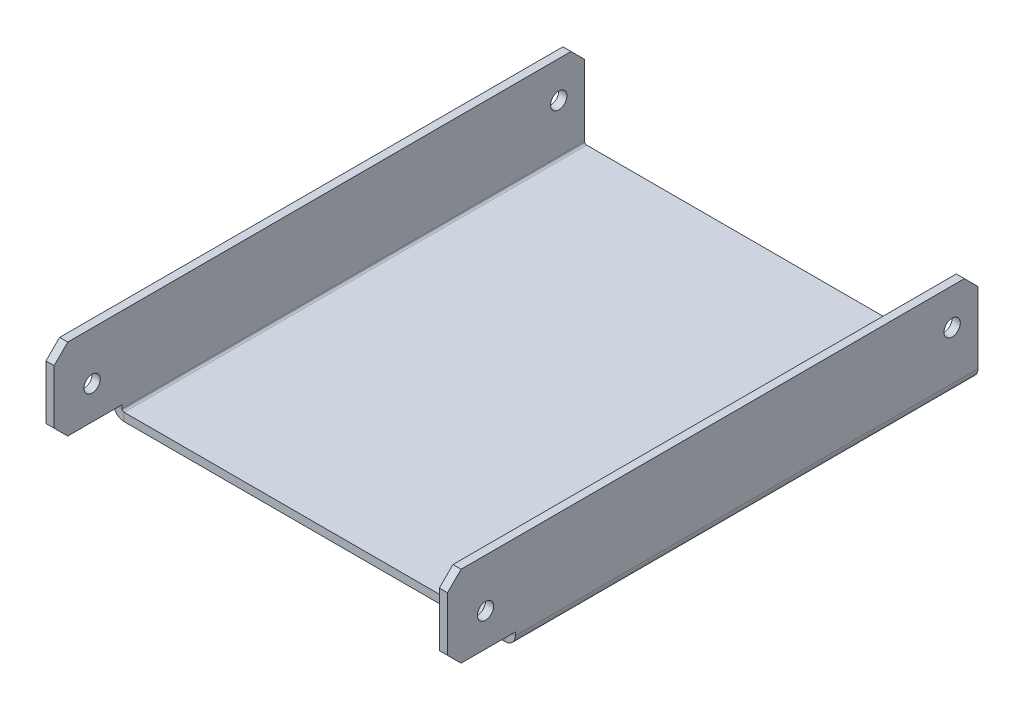
SolidWorks part; units mm, degrees
note: The reader was unsure of these and kept them because the rebuilt part matched: flange length of "Edge-Flange1".
ref_plane "정면" through (0, 0, 0) normal (0, 0, 1) x (1, 0, 0)
ref_plane "윗면" through (0, 0, 0) normal (0, 1, 0) x (1, 0, 0)
ref_plane "우측면" through (0, 0, 0) normal (1, 0, 0) x (0, 0, -1)
sketch "Sketch18" plane through (0, 0, 0) normal (0, 1, 0) x (1, 0, 0)
  line L1 (-148, -166.3369) -> (0, -166.3369)
  line L2 (-148, -166.3369) -> (-148, 39.1965)
  line L3 (-148, 39.1965) -> (0, 39.1965)
  line L4 (0, -166.3369) -> (0, 39.1965)
  dimension "D1" = 205.5334
  dimension "D2" = 148
base flange "Base-Flange1" sketch "Sketch18" thickness 3 reverse thickness direction no parameters "D1"=0.7366
edge flange "Edge-Flange1" sketch "Sketch25" flange profiles "Sketch25", "Sketch26" flange angle 90 flange length 35 flange position material inside bend radius 0.7366 thickness 3 relief rectangular parameters "D6"=10, "D8"=1
sketch "Sketch25" plane through (0, 0, 0) normal (-1, 0, 0) x (0, 0, 1)
  line L2 (-39.1965, 0) -> (-39.1965, 32)
  line L3 (-39.1965, 32) -> (166.3369, 32)
  line L4 (166.3369, 32) -> (166.3369, 0)
  line L14 (166.3369, 0) -> (-39.1965, 0) construction
  line L15 (166.3369, 0) -> (-39.1965, 0)
sketch "Sketch26" plane through (-148, 0, 0) normal (1, 0, 0) x (0, 0, -1)
  line L2 (-166.3369, 0) -> (-166.3369, 32)
  line L3 (-166.3369, 32) -> (39.1965, 32)
  line L4 (39.1965, 32) -> (39.1965, 0)
  line L10 (39.1965, 0) -> (-166.3369, 0) construction
  line L11 (39.1965, 0) -> (-166.3369, 0)
bend "EdgeBend1" bend radius 0.7366 bend angle 90 parameters "D5"=1
bend "EdgeBend2" bend radius 0.7366 bend angle 90 parameters "D5"=2
sketch "Sketch28" plane through (0, 0, 166.3369) normal (0, 0, 1) x (1, 0, 0)
  line L1 (-149, -6) -> (1, -6)
  line L2 (-149, -6) -> (-149, 2)
  line L3 (-149, 2) -> (1, 2)
  line L4 (1, -6) -> (1, 2)
  dimension "D1" = 8
  dimension "D2" = 150
extrude "Cut-Extrude2" cut sketch "Sketch28" against normal blind 25 normal cut yes
sketch "Sketch30" plane through (-148, 0, 0) normal (-1, 0, 0) x (0, 0, 1)
  line L0 (-39.1965, 0.7366) -> (-39.1965, 32) construction
  line L1 (-39.1965, 32) -> (166.3369, 32) construction
  line L2 (166.3369, 32) -> (166.3369, 2) construction
  circle A0 centre (152.3369, 14.23) radius 3
  circle A1 centre (-19.6665, 18.64) radius 3
  dimension "D1" = 6
  dimension "D2" = 6
  dimension "D4" = 13.36
  dimension "D5" = 14
  dimension "D6" = 17.77
  dimension "D3" = 19.53
extrude "Cut-Extrude3" cut sketch "Sketch30" against normal through all normal cut yes
sketch "Sketch31" plane through (0, 0, -39.1965) normal (0, 0, -1) x (-1, 0, 0)
  line L5 (153.8764, -3) -> (-3.5788, -3)
  line L6 (153.8764, -3) -> (153.8764, 37)
  line L7 (153.8764, 37) -> (-3.5788, 37)
  line L8 (-3.5788, -3) -> (-3.5788, 37)
extrude "Cut-Extrude4" cut sketch "Sketch31" against normal blind 10 normal cut yes
chamfer "Chamfer1" distance 5 angle 45 6 edges at (-1.5, 2, 166.3369) (-1.5, 32, 166.3369) (-146.5, 32, 166.3369) (-146.5, 32, -29.1965) (-1.5, 32, -29.1965) (-146.5, 2, 166.3369)
sketch "굽힘 선1" [suppressed] plane through (0, 0, 0) normal (0, 1, 0) x (1, 0, 0)
sketch "경계 상자1" [suppressed] plane through (0, 0, 0) normal (0, 1, 0) x (1, 0, 0)
sheet metal parameters "Sheet-Metal97" thickness 3 parameters "D1"=0.7366
flat pattern "Flat-Pattern97" [suppressed]
sketch "굽힘 선2" plane through (0, 0, 0) normal (0, 1, 0) x (1, 0, 0)
sketch3d "경계 상자2" [suppressed]
  line L0 (150, -166.3369, 0) -> (150, 39.1965, 0) construction
  line L1 (0, -166.3369, 0) -> (0, 39.1965, 0) construction
  line L2 (150, -166.3369, 0) -> (0, -166.3369, 0) construction
  line L3 (150, 39.1965, 0) -> (0, 39.1965, 0) construction
sheet metal parameters "Sheet-Metal98" thickness 3 parameters "D1"=0.7366
flat pattern "Flat-Pattern97" [suppressed]
sketch "굽힘 선2" plane through (0, 0, 0) normal (0, 1, 0) x (1, 0, 0)
  line L0 (-148.02, 39.1965) -> (-148.02, -166.3369) construction
  line L1 (-1.98, -166.3369) -> (-1.98, 39.1965) construction
  line L2 (-148.02, 39.1965) -> (-148.02, -166.3369) construction
  line L3 (-1.98, -166.3369) -> (-1.98, 39.1965) construction
sketch3d "경계 상자2" [suppressed]
  line L0 (-176.04, -166.3369, 0) -> (-176.04, 39.1965, 0) construction
  line L1 (26.04, -166.3369, 0) -> (26.04, 39.1965, 0) construction
  line L2 (-176.04, -166.3369, 0) -> (26.04, -166.3369, 0) construction
  line L3 (-176.04, 39.1965, 0) -> (26.04, 39.1965, 0) construction
bend of the flat pattern "Flatten-<EdgeBend1>1"
bend of the flat pattern "Flatten-<EdgeBend2>1"
sheet metal parameters "Sheet-Metal100" thickness 3 parameters "D1"=0.7366
flat pattern "Flat-Pattern97"
sketch "굽힘 선2" plane through (0, 0, 0) normal (0, 1, 0) x (1, 0, 0)
  line L0 (-137.02, 39.1965) -> (-137.02, -141.3369) construction
  line L1 (-1.98, -141.3369) -> (-1.98, 39.1965) construction
  line L2 (-137.02, 39.1965) -> (-137.02, -141.3369) construction
  line L3 (-1.98, -141.3369) -> (-1.98, 39.1965) construction
sketch3d "경계 상자2" [suppressed]
  line L0 (36.04, 39.1965, 0) -> (-175.04, 39.1965, 0) construction
  line L1 (36.04, -166.3369, 0) -> (-175.04, -166.3369, 0) construction
  line L2 (36.04, 39.1965, 0) -> (36.04, -166.3369, 0) construction
  line L3 (-175.04, 39.1965, 0) -> (-175.04, -166.3369, 0) construction
bend of the flat pattern "Flatten-<EdgeBend1>1"
bend of the flat pattern "Flatten-<EdgeBend2>1"
sheet metal parameters "Sheet-Metal101" thickness 3 parameters "D1"=0.7366
flat pattern "Flat-Pattern97"
sketch "굽힘 선2" plane through (0, 0, 0) normal (0, 1, 0) x (1, 0, 0)
  line L0 (-146.02, 39.1965) -> (-146.02, -166.3369) construction
  line L1 (-1.98, -141.3369) -> (-1.98, 39.1965) construction
  line L2 (-146.02, 39.1965) -> (-146.02, -166.3369) construction
  line L3 (-1.98, -141.3369) -> (-1.98, 39.1965) construction
sketch3d "경계 상자2" [suppressed]
  line L0 (36.04, 39.1965, 0) -> (-184.04, 39.1965, 0) construction
  line L1 (36.04, -166.3369, 0) -> (-184.04, -166.3369, 0) construction
  line L2 (36.04, 39.1965, 0) -> (36.04, -166.3369, 0) construction
  line L3 (-184.04, 39.1965, 0) -> (-184.04, -166.3369, 0) construction
bend of the flat pattern "Flatten-<EdgeBend1>1"
bend of the flat pattern "Flatten-<EdgeBend2>1"
sheet metal parameters "Sheet-Metal102" thickness 3 parameters "D1"=0.7366
flat pattern "Flat-Pattern97"
sketch "굽힘 선2" plane through (0, 0, 0) normal (0, 1, 0) x (1, 0, 0)
  line L0 (-146.02, 29.1965) -> (-146.02, -141.3369) construction
  line L1 (-1.98, -141.3369) -> (-1.98, 29.1965) construction
  line L2 (-146.02, 29.1965) -> (-146.02, -141.3369) construction
  line L3 (-1.98, -141.3369) -> (-1.98, 29.1965) construction
sketch3d "경계 상자2" [suppressed]
  line L0 (31.04, 29.1965, 0) -> (-179.04, 29.1965, 0) construction
  line L1 (31.04, -166.3369, 0) -> (-179.04, -166.3369, 0) construction
  line L2 (31.04, 29.1965, 0) -> (31.04, -166.3369, 0) construction
  line L3 (-179.04, 29.1965, 0) -> (-179.04, -166.3369, 0) construction
bend of the flat pattern "Flatten-<EdgeBend1>1"
bend of the flat pattern "Flatten-<EdgeBend2>1"
